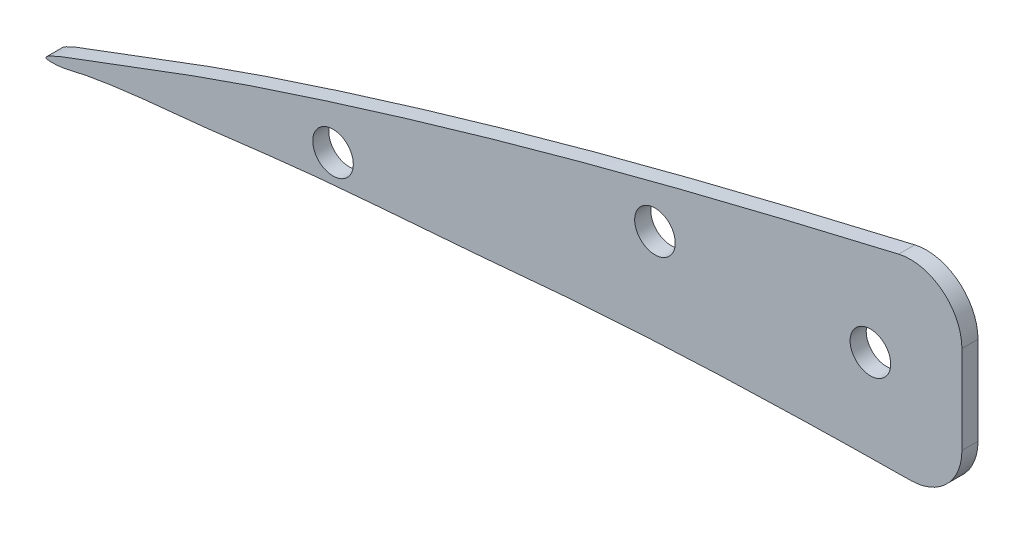
SolidWorks part; units mm, degrees
material "Balsa"
ref_plane "Front Plane" through (0, 0, 0) normal (0, 0, 1) x (1, 0, 0)
ref_plane "Top Plane" through (0, 0, 0) normal (0, 1, 0) x (1, 0, 0)
ref_plane "Right Plane" through (0, 0, 0) normal (1, 0, 0) x (0, 0, -1)
sketch "Sketch1" plane through (0, 0, 0) normal (0, 0, 1) x (1, 0, 0)
  line L0 (99.3264, 18.4044) -> (99.3264, -2.9864)
  line L1 (73.9264, 12.4163) -> (99.3264, -2.9864) construction
  line L8 (238.3754, -9.6537) -> (238.3754, -27.8289) construction
  line L9 (73.9264, -3.3744) -> (73.9264, 12.4163) construction
  line L10 (238.3754, -9.6537) -> (3.4483, -9.6537) construction
  line L11 (73.9264, -3.3744) -> (73.9264, 12.4163) construction
  line L12 (99.3264, 18.4044) -> (73.9264, -3.3744) construction
  spline S0 degree 3 poles (5.0476, -9.6537) (1.3045, -10.0425) (11.5033, -6.3535) (19.7236, -3.0928) (52.9152, 7.6459) (77.8898, 13.46) (99.3264, 18.4044) knots 0 0 0 0 0.059915 0.175786 0.369275 1 1 1 1
  spline S1 degree 3 poles (5.0476, -9.6537) (9.4826, -8.5461) (16.9885, -8.0769) (30.3366, -6.2544) (41.9467, -5.566) (65.8658, -3.2313) (83.9748, -3.0891) (99.3264, -2.9864) knots 0 0 0 0 0.144322 0.237948 0.427123 0.512832 1 1 1 1
  spline S6 degree 3 poles (5.0476, -9.6537) (9.4826, -8.5461) (16.9885, -8.0769) (30.3366, -6.2543) (41.9468, -5.5667) (60.7635, -3.7271) (83.9252, -2.9983) (119.6066, -2.8533) (155.1663, -4.9989) (188.2936, -10.0956) (210.9238, -14.2463) (226.8417, -14.3145) (237.449, -14.868) (238.3754, -9.6537) knots 0 0 0 0 0.057787 0.095275 0.171021 0.205339 0.335319 0.464904 0.658702 0.785512 0.893517 0.943092 1 1 1 1 construction
  spline S7 degree 3 poles (238.3754, -9.6537) (237.7653, -4.112) (231.8626, 3.793) (218.5807, 12.9188) (199.1338, 22.0262) (170.9048, 27.4643) (139.4251, 26.4056) (107.9057, 20.4989) (74.2413, 12.6461) (44.8793, 5.0523) (19.7218, -3.094) (11.5035, -6.3533) (1.3045, -10.0425) (5.0476, -9.6537) knots 0 0 0 0 0.060864 0.113688 0.188609 0.312909 0.448482 0.557612 0.691544 0.852438 0.929756 0.976058 1 1 1 1 construction
  dimension "D1" = 25.4
  dimension "D3" = 164.449
  dimension "D4" = 234.9271
extrude "Boss-Extrude1" add sketch "Sketch1" along normal blind 226.06
sketch "Sketch2" plane through (0, 0, 0) normal (0, 1, 0) x (1, 0, 0)
  line L0 (169.6815, 0) -> (169.6815, -226.06)
  line L1 (169.6815, -226.06) -> (73.1644, -226.06)
  line L2 (73.1644, -226.06) -> (73.1644, -197.485)
  line L3 (73.1644, -197.485) -> (93.7384, -197.485)
  line L4 (93.7384, -197.485) -> (93.7384, -28.575)
  line L5 (93.7384, -28.575) -> (73.1644, -28.575)
  line L6 (73.1644, -28.575) -> (73.1644, 0)
  line L7 (73.1644, 0) -> (169.6815, 0)
  line L8 (3.4109, -226.06) -> (99.3264, -226.06) construction
  line L9 (99.3264, 0) -> (3.4109, 0) construction
  line L10 (99.3264, -226.06) -> (99.3264, 0) construction
  dimension "D1" = 20.574
  dimension "D2" = 5.588
  dimension "D3" = 75.9431
  dimension "D4" = 28.575
  dimension "D5" = 0
  dimension "D6" = 0
extrude "Cut-Extrude1" cut sketch "Sketch2" against normal through all both and the other way through all
fillet "Fillet1" radius 5.08 6 edges at (73.1644, -3.3889, 14.2875) (73.1644, 12.236, 14.2875) (93.7384, -3.0267, 113.03) (93.7384, 17.1136, 113.03) (73.1644, -3.3889, 211.7725) (73.1644, 12.236, 211.7725)
sketch "Sketch4" plane through (0, 0, 0) normal (1, 0, 0) x (0, 0, -1)
  line L0 (-197.485, 2.0054) -> (-197.485, 10.7162) construction
  line L1 (-238.6023, -25.5438) -> (-197.485, -25.5438)
  line L2 (-238.6023, -25.5438) -> (-238.6023, 42.1009)
  line L3 (-238.6023, 42.1009) -> (-197.485, 42.1009)
  line L4 (-197.485, -25.5438) -> (-197.485, 42.1009)
  line L6 (-195.8975, 42.1009) -> (15.385, 42.1009)
  line L7 (-195.8975, 42.1009) -> (-195.8975, -39.6297)
  line L8 (-195.8975, -39.6297) -> (15.385, -39.6297)
  line L9 (15.385, 42.1009) -> (15.385, -39.6297)
  dimension "D1" = 1.5875
extrude "Cut-Extrude5" cut sketch "Sketch4" along normal through all
sketch "Sketch3" plane through (0, 0, 0) normal (0, 0, 1) x (1, 0, 0)
  line L8 (238.3754, -9.6537) -> (238.3754, -27.8289) construction
  circle A0 centre (84.7136, 5.8749) radius 2
  dimension "D1" = 4
extrude "Cut-Extrude2" cut sketch "Sketch3" along normal through all
sketch "Sketch5" plane through (0, 0, 197.485) normal (0, 0, 1) x (1, 0, 0)
  circle A2 centre (31.7176, -3.5577) radius 2
  circle A3 centre (63.4676, 5.5863) radius 2
  dimension "D1" = 4
  dimension "D2" = 26.67
  dimension "D3" = 58.42
  dimension "D4" = 6.096
  dimension "D5" = 15.24
extrude "Cut-Extrude6" cut sketch "Sketch5" against normal through all
